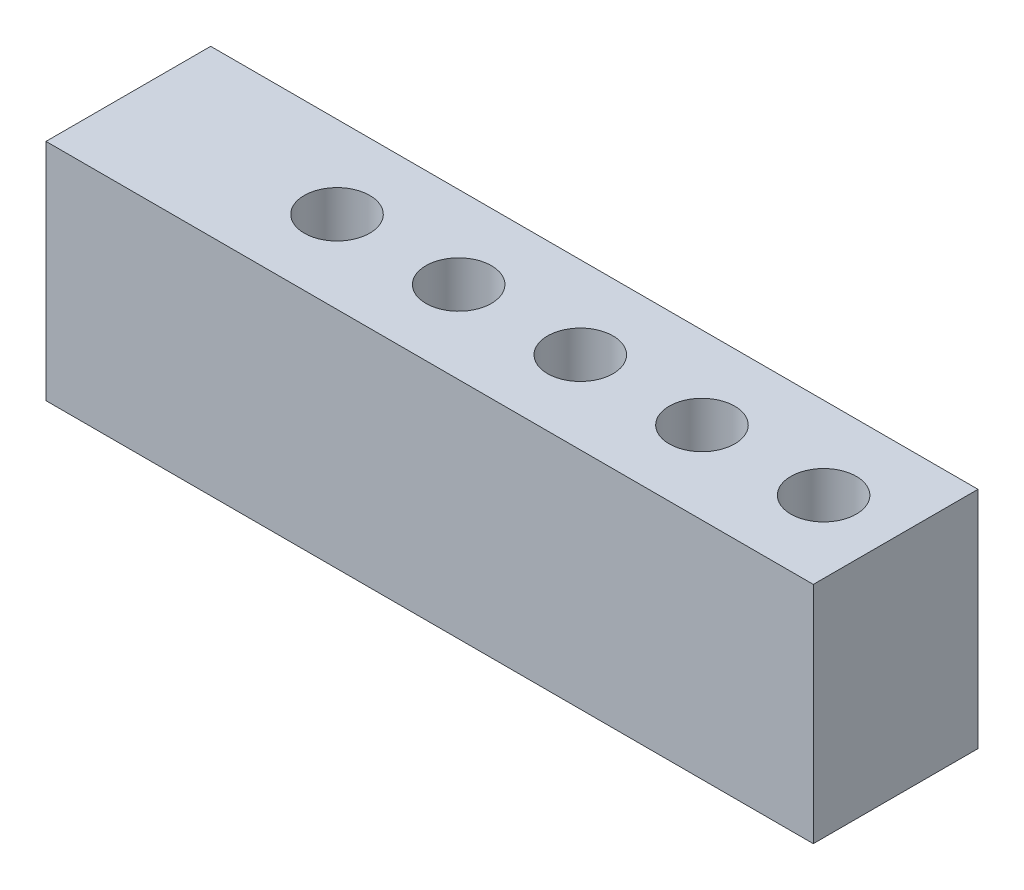
SolidWorks part; units mm, degrees
material "1060 Alloy"
ref_plane "Front Plane" through (0, 0, 0) normal (0, 0, 1) x (1, 0, 0)
ref_plane "Top Plane" through (0, 0, 0) normal (0, 1, 0) x (1, 0, 0)
ref_plane "Right Plane" through (0, 0, 0) normal (1, 0, 0) x (0, 0, -1)
sketch "Sketch4" plane through (0, 0, 0) normal (1, 0, 0) x (0, 0, -1)
  line L0 (0, 0) -> (11.176, 0) construction
  line L1 (-11.176, 15.24) -> (11.176, 15.24)
  line L2 (-11.176, 15.24) -> (-11.176, -15.24)
  line L3 (-11.176, -15.24) -> (11.176, -15.24)
  line L4 (11.176, 15.24) -> (11.176, -15.24)
  line L5 (0, 0) -> (-11.176, 0) construction
  line L6 (0, 0) -> (0, -15.24) construction
  line L7 (0, 0) -> (0, 15.24) construction
  dimension "D1" = 11.176
  dimension "D2" = 15.24
extrude "Boss-Extrude2" add sketch "Sketch4" along normal blind 104.14
sketch "Sketch5" plane through (0, 0, 0) normal (-1, 0, 0) x (0, 0, 1)
  line L0 (11.176, -15.24) -> (-11.176, -15.24) construction
  circle A0 centre (0, -1.9939) radius 5.08
  dimension "D1" = 10.16
  dimension "D2" = 8.1661
ref_plane "Plane2" through (100.33, 0, 0) normal (1, 0, 0) x (0, 0, -1)
extrude "Cut-Extrude2" cut sketch "Sketch5" against normal up to surface (100.33 mm away) up to plane "Plane2"
ref_plane "Plane3" through (28.321, 0, 0) normal (1, 0, 0) x (0, 0, -1)
sketch "Sketch9" plane through (0, 15.24, 0) normal (0, 1, 0) x (1, 0, 0)
  line L0 (28.321, -12.2936) -> (28.321, 12.2936) construction
  line L2 (0, 0) -> (104.14, 0) construction
  line L3 (0, 11.176) -> (0, -11.176) construction
  line L4 (104.14, 11.176) -> (104.14, -11.176) construction
  circle A0 centre (28.321, 0) radius 4.445
  dimension "D1" = 8.89
extrude "Cut-Extrude5" cut sketch "Sketch9" against normal up to next
pattern_linear "LPattern1" count 5 spacing 16.51 along (1, 0, 0) of "Cut-Extrude5"
sketch "Sketch14" plane through (0, 0, 0) normal (-1, 0, 0) x (0, 0, 1)
  line L0 (0, 3.0861) -> (0, -7.0739) construction
  circle A0 centre (0, -1.9939) radius 5.08 construction
  circle A1 centre (0, -1.9939) radius 5.08 construction
  circle A2 centre (0, -1.9939) radius 7.1438
  dimension "D1" = 14.2875
extrude "Cut-Extrude7" cut sketch "Sketch14" against normal blind 20.066
equation "\"A\"= 100"
equation "\"B\"= 100"
equation "\"C\"= 100"
equation "\"D\"= 100"
equation "\"E\"= 100"
